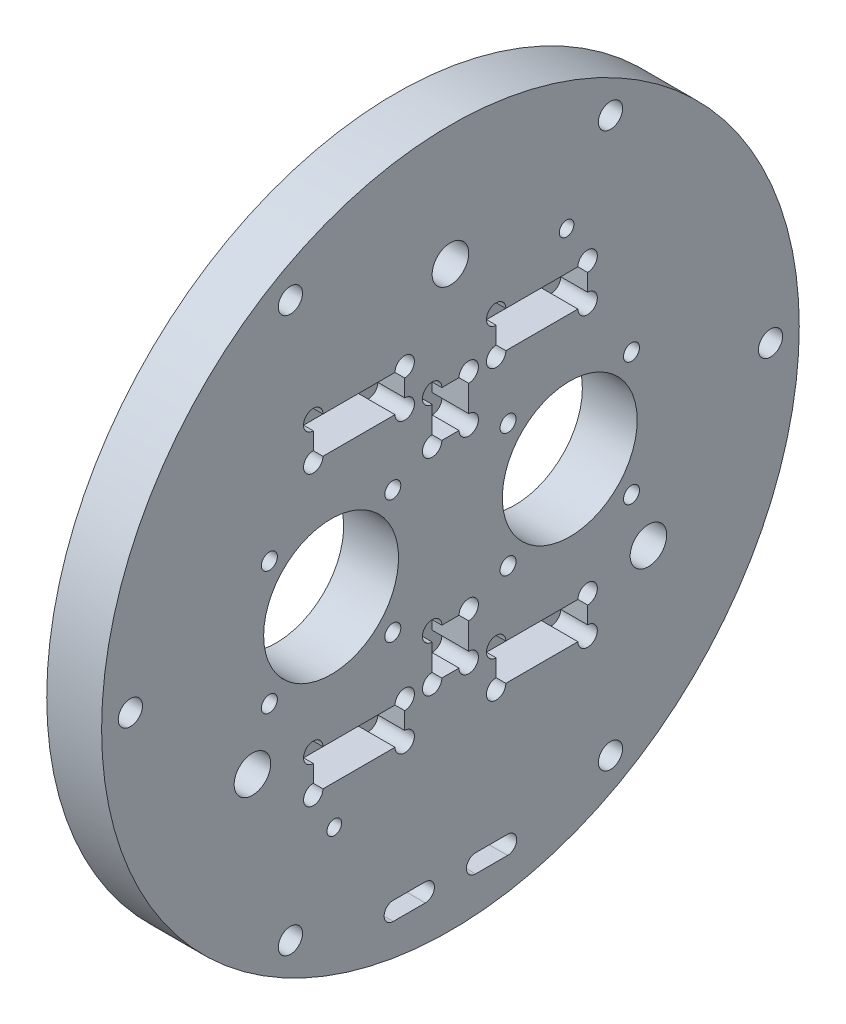
SolidWorks part; units mm, degrees
ref_plane "Front Plane" through (0, 0, 0) normal (0, 0, 1) x (1, 0, 0)
ref_plane "Top Plane" through (0, 0, 0) normal (0, 1, 0) x (1, 0, 0)
ref_plane "Right Plane" through (0, 0, 0) normal (1, 0, 0) x (0, 0, -1)
sketch "Sketch1" plane through (0, 0, 0) normal (1, 0, 0) x (0, 0, -1)
  line L0 (0, -76.29) -> (0, 76.29) construction
  line L1 (-76.29, 0) -> (76.29, 0) construction
  line L2 (26.1, 0) -> (39.5969, 13.4969) construction
  circle A0 centre (0, 0) radius 76.29
  circle A1 centre (0, 50) radius 4
  circle A2 centre (43.3013, -25) radius 4
  circle A3 centre (-43.3013, -25) radius 4
  circle A4 centre (26.1, 0) radius 14.75
  circle A5 centre (-26.1, 0) radius 14.75
  circle A6 centre (39.5969, 13.4969) radius 1.75
  circle A7 centre (39.5969, -13.4969) radius 1.75
  circle A8 centre (12.6031, -13.4969) radius 1.75
  circle A9 centre (12.6031, 13.4969) radius 1.75
  circle A10 centre (-39.5969, -13.4969) radius 1.75
  circle A11 centre (-12.6031, -13.4969) radius 1.75
  circle A12 centre (-12.6031, 13.4969) radius 1.75
  circle A13 centre (-39.5969, 13.4969) radius 1.75
  circle A14 centre (26.1, 0) radius 22.1 construction
  circle A15 centre (-26.1, 0) radius 22.1 construction
  point P12 (0, 0)
  point P29 (26.1, 0)
  point P37 (-4, 0)
  point P40 (4, 0)
  dimension "D1" = 152.58
  dimension "D2" = 8
  dimension "D5" = 29.5
  dimension "D7" = 3.5
  dimension "D11" = 44.2
  dimension "D3" = 50
  dimension "D4" = 3
  dimension "D6" = 8
  dimension "D8" = 19.0875
  dimension "D10" = 45
  dimension "D9" = 4
extrude "Boss-Extrude1" add sketch "Sketch1" along normal blind 12
sketch "Sketch2" plane through (12, 0, 0) normal (1, 0, 0) x (0, 0, -1)
  line L0 (-97.5918, 0) -> (102.3086, 0) construction
  line L1 (0, 96.3466) -> (0, -103.9448) construction
  line L2 (10, -27.5) -> (10, -35.5)
  line L3 (-30, -27.5) -> (-10, -27.5)
  line L4 (-30, -27.5) -> (-30, -35.5)
  line L5 (-30, -35.5) -> (-10, -35.5)
  line L6 (-10, -27.5) -> (-10, -35.5)
  line L7 (30, -27.5) -> (10, -27.5)
  line L8 (30, -27.5) -> (30, -35.5)
  line L9 (30, -35.5) -> (10, -35.5)
  line L10 (-30, 27.5) -> (-30, 35.5)
  line L11 (-30, 35.5) -> (-10, 35.5)
  line L12 (-10, 27.5) -> (-10, 35.5)
  line L13 (-30, 27.5) -> (-10, 27.5)
  line L14 (10, 27.5) -> (10, 35.5)
  line L15 (30, 35.5) -> (10, 35.5)
  line L16 (30, 27.5) -> (10, 27.5)
  line L17 (30, 27.5) -> (30, 35.5)
  line L18 (-4, -17.5) -> (4, -17.5)
  line L19 (-4, 27.5) -> (4, 27.5)
  line L20 (-4, 27.5) -> (-4, 17.5)
  line L21 (-4, 17.5) -> (4, 17.5)
  line L22 (4, 27.5) -> (4, 17.5)
  line L23 (-4, -27.5) -> (-4, -17.5)
  line L24 (-4, -27.5) -> (4, -27.5)
  line L25 (4, -27.5) -> (4, -17.5)
  line L26 (27.8787, -35.5) -> (30, -33.3787) construction
  line L27 (-42.3534, -68.29) -> (39.6493, -68.29) construction
  line L28 (-5.5, -68.29) -> (-5.5, -64.29)
  line L29 (12.5, -68.29) -> (5.5, -68.29)
  line L30 (12.5, -68.29) -> (12.5, -64.29)
  line L31 (12.5, -64.29) -> (5.5, -64.29)
  line L32 (5.5, -68.29) -> (5.5, -64.29)
  line L33 (-12.5, -64.29) -> (-5.5, -64.29)
  line L34 (-12.5, -68.29) -> (-12.5, -64.29)
  line L35 (-12.5, -68.29) -> (-5.5, -68.29)
  circle A0 centre (30, -35.5) radius 2.1213 construction
  circle A1 centre (0, 0) radius 76.29 construction
  point P23 (0, 27.5)
  point P31 (30, -33.3787)
  point P32 (0, -76.29)
  point P33 (27.8787, -35.5)
  dimension "D1" = 27.5
  dimension "D2" = 8
  dimension "D3" = 20
  dimension "D4" = 20
  dimension "D5" = 8
  dimension "D6" = 10
  dimension "D7" = 8
  dimension "D8" = 4
  dimension "D9" = 7
  dimension "D10" = 25
extrude "Cut-Extrude1" cut sketch "Sketch2" against normal blind 8
sketch "Sketch3" plane through (0, 0, 0) normal (-1, 0, 0) x (0, 0, 1)
  circle A0 centre (-70, 0) radius 2.65
  circle A1 centre (-35, 60.6218) radius 2.65
  circle A2 centre (35, 60.6218) radius 2.65
  circle A3 centre (70, 0) radius 2.65
  circle A4 centre (35, -60.6218) radius 2.65
  circle A5 centre (-35, -60.6218) radius 2.65
  point P16 (0, 0)
  dimension "D2" = 5.3
  dimension "D1" = 70
  dimension "D3" = 6
extrude "Cut-Extrude2" cut sketch "Sketch3" against normal up to next
sketch "Sketch4" plane through (12, 0, 0) normal (1, 0, 0) x (0, 0, -1)
  line L0 (12.5, -68.29) -> (12.5, -64.29) construction
  line L2 (5.5, -64.29) -> (5.5, -68.29) construction
  line L3 (-5.5, -68.29) -> (-5.5, -64.29) construction
  line L4 (-12.5, -64.29) -> (-12.5, -68.29) construction
  circle A0 centre (-10, -35.5) radius 2.1213
  circle A1 centre (-10, -27.5) radius 2.1213
  circle A2 centre (-30, -27.5) radius 2.1213
  circle A3 centre (-30, -35.5) radius 2.1213
  circle A4 centre (12.5, -66.29) radius 2
  circle A5 centre (5.5, -66.29) radius 2
  circle A6 centre (-5.5, -66.29) radius 2
  circle A7 centre (-12.5, -66.29) radius 2
  circle A12 centre (10, -35.5) radius 2.1213
  circle A13 centre (10, -27.5) radius 2.1213
  circle A14 centre (30, -27.5) radius 2.1213
  circle A15 centre (30, -35.5) radius 2.1213
  circle A16 centre (4, -27.5) radius 2.1213
  circle A17 centre (-4, -27.5) radius 2.1213
  circle A18 centre (-4, -17.5) radius 2.1213
  circle A19 centre (4, -17.5) radius 2.1213
  circle A20 centre (4, 27.5) radius 2.1213
  circle A21 centre (-4, 27.5) radius 2.1213
  circle A22 centre (-4, 17.5) radius 2.1213
  circle A23 centre (4, 17.5) radius 2.1213
  circle A24 centre (10, 27.5) radius 2.1213
  circle A25 centre (10, 35.5) radius 2.1213
  circle A26 centre (30, 35.5) radius 2.1213
  circle A27 centre (30, 27.5) radius 2.1213
  circle A28 centre (-10, 35.5) radius 2.1213
  circle A29 centre (-10, 27.5) radius 2.1213
  circle A30 centre (-30, 27.5) radius 2.1213
  circle A31 centre (-30, 35.5) radius 2.1213
  point P2 (-12.1213, -35.5)
  point P5 (-10, -33.3787)
  dimension "D1" = 3
extrude "Cut-Extrude3" cut sketch "Sketch4" against normal up to surface (8 mm away) up to face at (4, -31.5, 20)
sketch "Sketch5" plane through (0, 0, 0) normal (-1, 0, 0) x (0, 0, 1)
  line L0 (35, -60.6218) -> (-35, 60.6218) construction
  line L1 (0, 113.7201) -> (0, -122.5246) construction
  line L2 (-128.5049, 0) -> (121.7105, 0) construction
  circle A0 centre (35, -60.6218) radius 2.65 construction
  circle A1 centre (25.4034, -44) radius 1.6
  circle A2 centre (-25.4034, 44) radius 1.6
  point P12 (0, 0)
  dimension "D2" = 3.2
  dimension "D1" = 2
  dimension "D3" = 44
  dimension "D4" = 50.8068
extrude "Cut-Extrude4" cut sketch "Sketch5" against normal up to next
